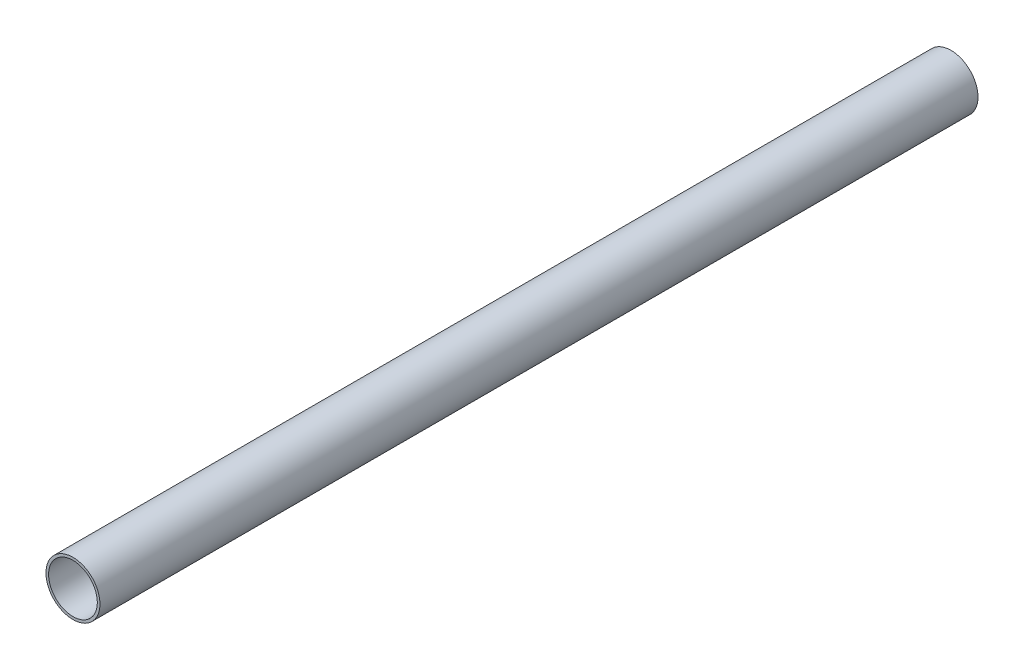
SolidWorks part; units mm, degrees
material "Brass"
ref_plane "Front Plane" through (0, 0, 0) normal (0, 0, 1) x (1, 0, 0)
ref_plane "Top Plane" through (0, 0, 0) normal (0, 1, 0) x (1, 0, 0)
ref_plane "Right Plane" through (0, 0, 0) normal (1, 0, 0) x (0, 0, -1)
sketch "Sketch1" plane through (0, 0, 0) normal (0, 0, 1) x (1, 0, 0)
  circle A0 centre (0, 0) radius 0.375
  circle A1 centre (0, 0) radius 0.415
  dimension "D1" = 0.83
  dimension "D2" = 0.75
extrude "Boss-Extrude1" add sketch "Sketch1" along normal blind 13.5
scale "Scale1" scale about centroid uniform scaling yes scale factor 6
